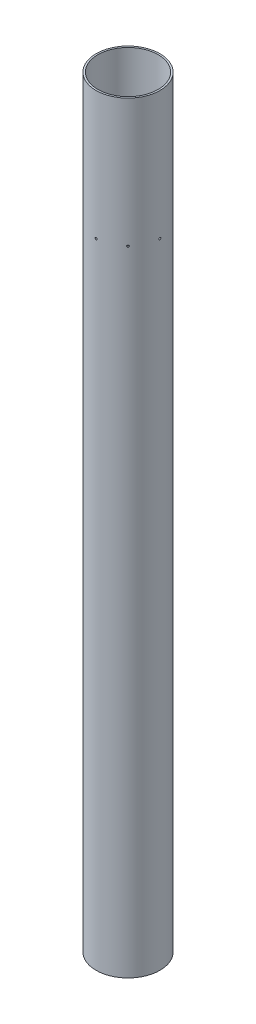
SolidWorks part; units mm, degrees
ref_plane "Front Plane" through (0, 0, 0) normal (0, 0, 1) x (1, 0, 0)
ref_plane "Top Plane" through (0, 0, 0) normal (0, 1, 0) x (1, 0, 0)
ref_plane "Right Plane" through (0, 0, 0) normal (1, 0, 0) x (0, 0, -1)
sketch "Sketch1" plane through (0, 0, 0) normal (0, 1, 0) x (1, 0, 0)
  circle A0 centre (0, 0) radius 53.721
  circle A1 centre (0, 0) radius 50.8
  dimension "D1" = 107.442
  dimension "D2" = 101.6
extrude "Boss-Extrude1" add sketch "Sketch1" along normal blind 1282.7
ref_plane "Plane1" through (0, 0, 53.721) normal (0, 0, 1) x (1, 0, 0)
sketch "Sketch2" plane through (0, 0, 53.721) normal (0, 0, 1) x (1, 0, 0)
  circle A0 centre (0, 1066.8) radius 1.6383
  dimension "D1" = 3.2766
  dimension "D2" = 1066.8
extrude "Cut-Extrude1" cut sketch "Sketch2" against normal up to next
pattern_circular "CirPattern1" count 8 over 360 about axis through (0, 1282.7, 0) along (0, -1, 0) of "Cut-Extrude1"
